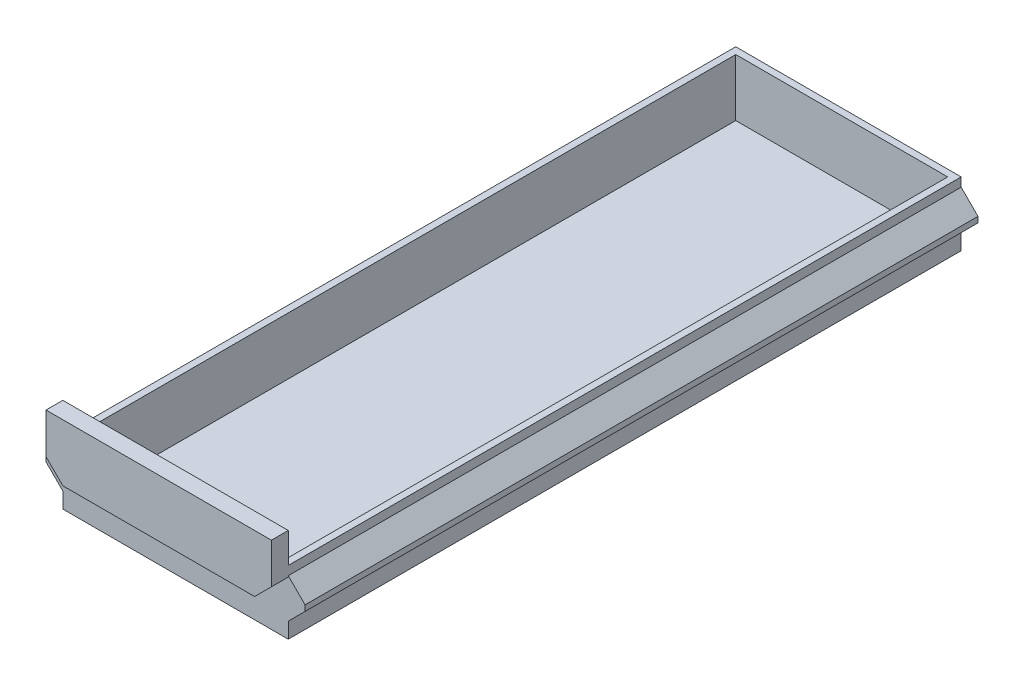
SolidWorks part; units mm, degrees
ref_plane "前视基准面" through (0, 0, 0) normal (0, 0, 1) x (1, 0, 0)
ref_plane "上视基准面" through (0, 0, 0) normal (0, 1, 0) x (1, 0, 0)
ref_plane "右视基准面" through (0, 0, 0) normal (1, 0, 0) x (0, 0, -1)
other "Configuration Table"
sketch "草图1" plane through (0, 0, 0) normal (0, 0, 1) x (1, 0, 0)
  line L0 (-73, 28) -> (-6, 28)
  line L1 (-73, 28) -> (-73, 32.6569)
  line L2 (-78, 37.6569) -> (-78, 39.3532)
  line L3 (-78, 39.3532) -> (-73, 44.3532)
  line L4 (-73, 44.3532) -> (-73, 47)
  line L5 (-77, 47) -> (-74, 47) construction
  line L6 (-73, 47) -> (-6, 47)
  line L7 (-39.5, 47) -> (-39.5, 2.5589) construction
  line L9 (-83, 41) -> (-77, 47) construction
  line L10 (-83, 37) -> (-83, 41) construction
  line L11 (-74, 3) -> (-74, 26) construction
  line L12 (-73, 32.6569) -> (-78, 37.6569)
  line L16 (-77, 31) -> (-83, 37) construction
  line L17 (-6, 32.6569) -> (-1, 37.6569)
  line L18 (-6, 44.3532) -> (-6, 47)
  line L19 (-1, 39.3532) -> (-6, 44.3532)
  line L20 (-1, 37.6569) -> (-1, 39.3532)
  line L21 (-6, 28) -> (-6, 32.6569)
  point P25 (-39.5, 28)
  dimension "D1" = 19
  dimension "D2" = 1
  dimension "D3" = 5
  dimension "D4" = 4.7
  dimension "D5" = 1
  dimension "D6" = 4
  dimension "D7" = 77
extrude "凸台-拉伸1" add sketch "草图1" against normal blind 200
sketch "草图2" plane through (0, 47, 0) normal (0, 1, 0) x (1, 0, 0)
  line L8 (-71, 2) -> (-8, 2)
  line L9 (-8, 2) -> (-8, 198)
  line L10 (-8, 198) -> (-71, 198)
  line L11 (-71, 198) -> (-71, 2)
  line L12 (-71, 2) -> (-8, 2)
  line L13 (-8, 2) -> (-8, 198)
  line L14 (-8, 198) -> (-71, 198)
  line L15 (-71, 198) -> (-71, 2)
  dimension "D1" = 2
extrude "切除-拉伸1" cut sketch "草图2" against normal offset from surface (17 mm away) 2 up to face at (-39.5, 28, -100)
sketch "草图3" plane through (0, 0, 0) normal (0, 0, 1) x (1, 0, 0)
  line L0 (87.5, 56) -> (-87.5, 56) construction
  line L1 (-73, 39) -> (-6, 39)
  line L2 (-73, 39) -> (-73, 56)
  line L3 (-73, 56) -> (-6, 56)
  line L4 (-6, 39) -> (-6, 56)
  line L5 (-73, 47) -> (-73, 44.3532) construction
  line L6 (-6, 44.3532) -> (-6, 47) construction
  line L7 (-6, 47) -> (-73, 47) construction
  dimension "D1" = 8
extrude "凸台-拉伸2" add sketch "草图3" along normal blind 5
chamfer "倒角1" distance 5 angle 45 2 edges at (-6, 39, 2.5) (-73, 39, 2.5)
